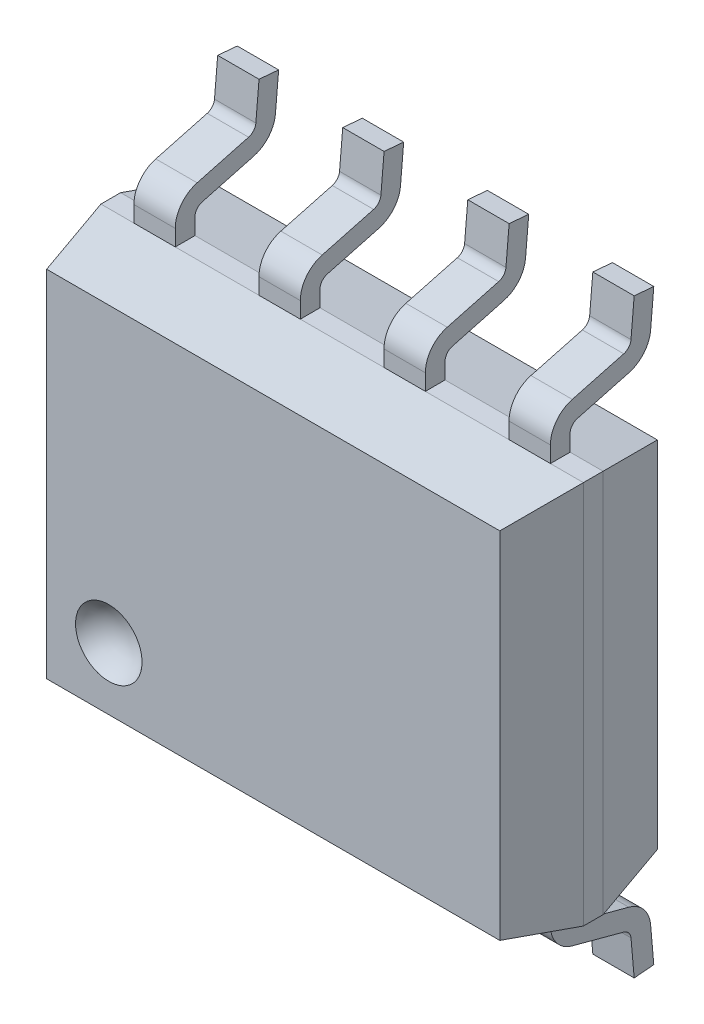
SolidWorks part; units mm, degrees
ref_plane "Top Plane" through (0, 0, 0) normal (0, 0, 1) x (1, 0, 0)
ref_plane "Front Plane" through (0, 0, 0) normal (0, 1, 0) x (1, 0, 0)
ref_plane "Right Plane" through (0, 0, 0) normal (1, 0, 0) x (0, 0, -1)
ref_axis "CenterAxis" through (0, 0, -0.0875) along (0, 0, 1)
ref_plane "Pin1Plane" through (-2.115, 0, 0) normal (1, 0, 0) x (0, 0, -1)
sketch "BodyWxH" plane through (0, 0, 0) normal (1, 0, 0) x (0, 0, -1)
  line L0 (0, 2.695) -> (0, -2.695) construction
  line L1 (-1.75, 1.95) -> (-0.15, 1.95)
  line L2 (-1.75, 1.95) -> (-1.75, -1.95)
  line L3 (-1.75, -1.95) -> (-0.15, -1.95)
  line L4 (-0.15, 1.95) -> (-0.15, -1.95)
  line L6 (-1.75, 0) -> (-0.15, 0) construction
  line L7 (0.0875, 0) -> (-1.8375, 0) construction
  dimension "W" = 3.9
  dimension "SO" = 0.15
  dimension "HMax" = 1.75
extrude "Boss-Body" add sketch "BodyWxH" along normal mid plane 4.9
chamfer "Chamfer1" distance 0.7 angle 12 8 edges at (0, -1.95, 0.15) (2.45, 0, 0.15) (0, 1.95, 0.15) (-2.45, 0, 0.15) (0, 1.95, 1.75) (2.45, 0, 1.75) (0, -1.95, 1.75) (-2.45, 0, 1.75) first distance on face at (0, -1.95, 0.95) first distance on face at (2.45, 0, 0.95) first distance on face at (0, 1.95, 0.95) first distance on face at (-2.45, 0, 0.95)
sketch "LeadCross" plane through (-2.115, 0, 0) normal (1, 0, 0) x (0, 0, -1)
  line L0 (0, -2.9826) -> (-0.1992, -3)
  line L1 (-0.1992, -3) -> (-0.2315, -2.6311)
  line L2 (-0.3053, -2.5432) -> (-0.8276, -2.4032)
  line L3 (-1.05, -2.1134) -> (-1.05, 2.1134)
  line L4 (-0.8276, 2.4032) -> (-0.3053, 2.5432)
  line L5 (-0.2315, 2.6311) -> (-0.1992, 3)
  line L6 (-0.1992, 3) -> (0, 2.9826)
  line L7 (0, 2.9826) -> (-0.0323, 2.6136)
  line L8 (-0.2535, 2.35) -> (-0.7759, 2.21)
  line L9 (-0.85, 2.1134) -> (-0.85, -2.1134)
  line L10 (-0.7759, -2.21) -> (-0.2535, -2.35)
  line L11 (-0.0323, -2.6136) -> (0, -2.9826)
  line L12 (0, 2.695) -> (0, -2.695) construction
  line L13 (-0.95, 0) -> (0, 0) construction
  line L14 (0.9625, 0) -> (-0.9625, 0) construction
  line L15 (-0.95, -0.9329) -> (-0.95, 0.9329) construction
  arc A0 (-0.0323, 2.6136) -> (-0.2535, 2.35) centre (-0.3311, 2.6398) cw
  arc A1 (-0.3053, 2.5432) -> (-0.2315, 2.6311) centre (-0.3311, 2.6398) ccw
  arc A2 (-0.2535, -2.35) -> (-0.0323, -2.6136) centre (-0.3311, -2.6398) cw
  arc A3 (-0.2315, -2.6311) -> (-0.3053, -2.5432) centre (-0.3311, -2.6398) ccw
  arc A4 (-0.85, -2.1134) -> (-0.7759, -2.21) centre (-0.75, -2.1134) ccw
  arc A5 (-0.8276, -2.4032) -> (-1.05, -2.1134) centre (-0.75, -2.1134) cw
  arc A6 (-1.05, 2.1134) -> (-0.8276, 2.4032) centre (-0.75, 2.1134) cw
  arc A7 (-0.7759, 2.21) -> (-0.85, 2.1134) centre (-0.75, 2.1134) ccw
  dimension "D2" = 5
  dimension "BendRadius" = 0.1
  dimension "LeadThickness" = 0.2
  dimension "ToeLength" = 0.65
  dimension "D4" = 75
  dimension "MidPlane" = 0.95
  dimension "LeadSpan" = 6
extrude "Pins" add sketch "LeadCross" along normal blind 0.42
pattern_linear "PatternLeads" count 4 along (1, 0, 0) of "Pins"
ref_plane "Pin1MarkPlane" through (-1.67, 0, 0) normal (1, 0, 0) x (0, 0, -1)
sketch "Pin1Indent" plane through (-1.67, 0, 0) normal (1, 0, 0) x (0, 0, -1)
  line L0 (-1.945, -0.78) -> (-1.945, -1.56) construction
  line L1 (0, 2.695) -> (0, -2.695) construction
  line L2 (-1.945, -1.17) -> (-1.555, -1.17) construction
  line L3 (0.9625, 0) -> (-0.9625, 0) construction
  line L4 (-1.945, -0.78) -> (-1.945, -1.56)
  arc A1 (-1.945, -1.56) -> (-1.945, -0.78) centre (-1.945, -1.17) ccw
  dimension "CutHeight" = 1.945
  dimension "CutSize" = 0.78
  dimension "CutOffset" = 1.17
revolve "Cut-Pin1Indent" cut sketch "Pin1Indent" angle 360 mid plane about L4
equation "\"D1@Pin1Plane\" = (\"D1@PatternLeads\"-1)*\"LeadPitch@PatternLeads\"/2+(\"LeadWidth@Pins\"/2) ' 1st pin edge plane"
equation "\"D1@Pin1MarkPlane\" = \"D1@Boss-Body\"/2-(\"W@BodyWxH\"*0.2) ' Pin 1 dent lies along this plane"
equation "\"CutSize@Pin1Indent\" = \"W@BodyWxH\"*0.2 ' Dent radius is half this value"
equation "\"CutOffset@Pin1Indent\" = \"W@BodyWxH\"/2-(\"W@BodyWxH\"*0.2) ' Dent distance from the center line"
equation "\"CutHeight@Pin1Indent\" = \"HMax@BodyWxH\"+(\"CutSize@Pin1Indent\"/4) ' Dent is cut by sphere this high"
equation "\"MidPlane@LeadCross\" = (\"HMax@BodyWxH\"+\"SO@BodyWxH\")/2"
equation "\"D1@Chamfer1\" = (\"HMax@BodyWxH\"-\"SO@BodyWxH\"-\"LeadThickness@LeadCross\")/2"
